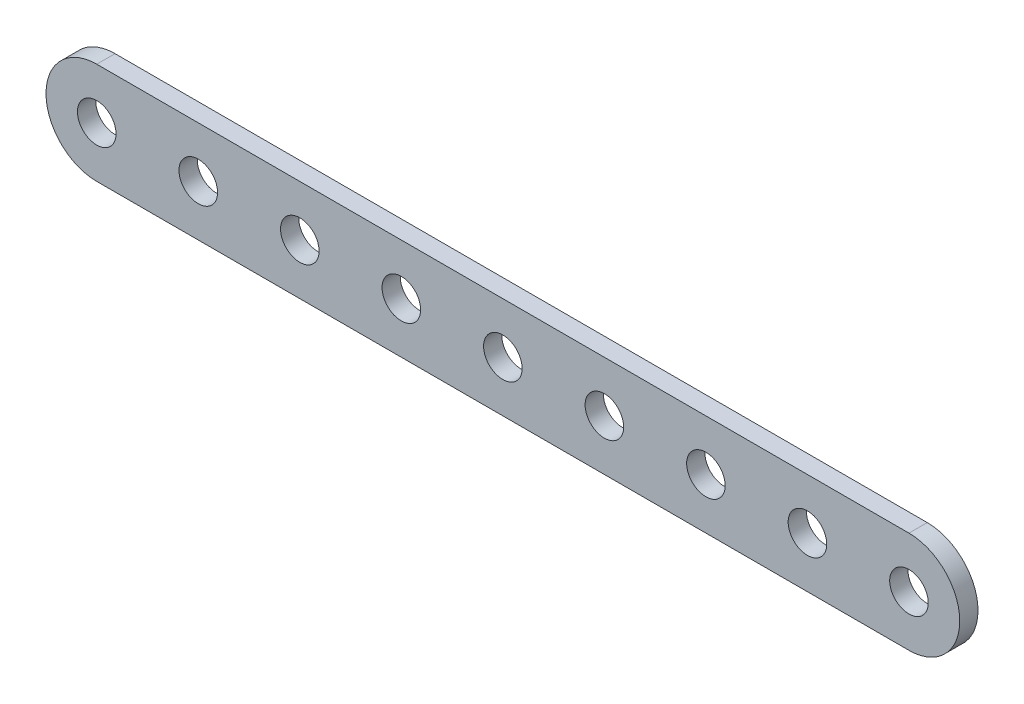
SolidWorks part; units mm, degrees
ref_plane "Front Plane" through (0, 0, 0) normal (0, 0, 1) x (1, 0, 0)
ref_plane "Top Plane" through (0, 0, 0) normal (0, 1, 0) x (1, 0, 0)
ref_plane "Right Plane" through (0, 0, 0) normal (1, 0, 0) x (0, 0, -1)
sketch "Sketch1" plane through (0, 0, 0) normal (0, 0, 1) x (1, 0, 0)
  line L0 (-50.8, 0) -> (50.8, 0) construction
  line L1 (-50.8, 6.35) -> (50.8, 6.35)
  line L2 (-50.8, -6.35) -> (50.8, -6.35)
  arc A0 (-50.8, 6.35) -> (-50.8, -6.35) centre (-50.8, 0) ccw
  arc A1 (50.8, -6.35) -> (50.8, 6.35) centre (50.8, 0) ccw
  point P2 (0, 0)
  dimension "D2" = 6.35
  dimension "D1" = 101.6
extrude "Boss-Extrude1" add sketch "Sketch1" along normal blind 2.286
sketch "Sketch2" plane through (0, 0, 2.286) normal (0, 0, 1) x (1, 0, 0)
  circle A0 centre (-50.8, 0) radius 2.413
  dimension "D1" = 4.826
extrude "Cut-Extrude1" cut sketch "Sketch2" against normal through all
pattern_linear "LPattern1" count 9 spacing 12.7 along (1, 0, 0) of "Cut-Extrude1"
